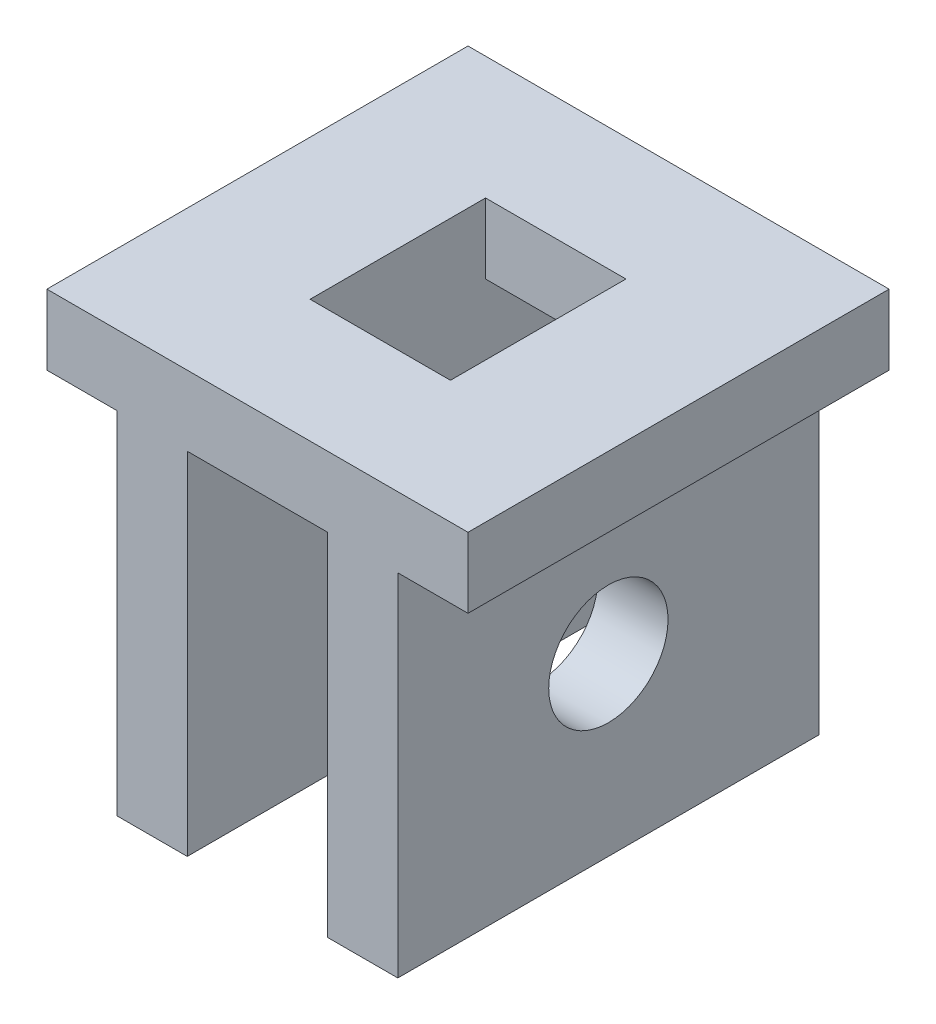
SolidWorks part; units mm, degrees
ref_plane "Front Plane" through (0, 0, 0) normal (0, 0, 1) x (1, 0, 0)
ref_plane "Top Plane" through (0, 0, 0) normal (0, 1, 0) x (1, 0, 0)
ref_plane "Right Plane" through (0, 0, 0) normal (1, 0, 0) x (0, 0, -1)
sketch "Sketch2" plane through (0, 0, 0) normal (0, 1, 0) x (1, 0, 0)
  line L1 (-3, 3) -> (0, 3)
  line L2 (-3, 3) -> (-3, 0)
  line L3 (-3, 0) -> (0, 0)
  line L4 (0, 3) -> (0, 0)
  dimension "D1" = 3
  dimension "D2" = 3
extrude "Boss-Extrude1" add sketch "Sketch2" along normal blind 3
sketch "Sketch3" plane through (0, 0, 0) normal (0, -1, 0) x (-1, 0, 0)
  line L0 (3, 0) -> (0, 0) construction
  line L1 (1, 0) -> (2, 0)
  line L2 (1, 0) -> (1, 3)
  line L3 (1, 3) -> (2, 3)
  line L4 (2, 0) -> (2, 3)
  line L5 (0, 3) -> (3, 3) construction
  line L7 (0, 0) -> (0.5, 0)
  line L8 (0, 0) -> (0, 3)
  line L9 (0, 3) -> (0.5, 3)
  line L10 (0.5, 0) -> (0.5, 3)
  line L11 (2.5, 0) -> (3, 0)
  line L12 (2.5, 0) -> (2.5, 3)
  line L13 (2.5, 3) -> (3, 3)
  line L14 (3, 0) -> (3, 3)
  point P8 (1.5, 3)
  point P9 (1.5, 3)
  dimension "D1" = 1
  dimension "D2" = 0.5
  dimension "D3" = 0.5
extrude "Cut-Extrude1" cut sketch "Sketch3" against normal blind 2.5
sketch "Sketch5" plane through (-0.5, 0, 0) normal (1, 0, 0) x (0, 0, -1)
  line L0 (0, 0) -> (3, 0) construction
  circle A0 centre (1.5, 1.25) radius 0.425
  point P4 (1.5, 0)
  dimension "D2" = 0.85
  dimension "D1" = 1.25
extrude "Cut-Extrude2" cut sketch "Sketch5" against normal through all both and the other way through all
sketch "Sketch6" plane through (0, 3, 0) normal (0, 1, 0) x (1, 0, 0)
  line L0 (0, 3) -> (-3, 3) construction
  line L1 (-2, 2.125) -> (-1, 2.125)
  line L2 (-2, 2.125) -> (-2, 0.875)
  line L3 (-2, 0.875) -> (-1, 0.875)
  line L4 (-1, 2.125) -> (-1, 0.875)
  line L5 (0, 0) -> (0, 3) construction
  point P6 (-1.5, 3)
  point P7 (-1.5, 2.125)
  point P10 (0, 1.5)
  point P11 (-1, 1.5)
  dimension "D1" = 1
  dimension "D2" = 1.25
extrude "Cut-Extrude3" cut sketch "Sketch6" against normal through all both contours L4 L1 L2 L3 region at (-1.5, 3, -1.5)
